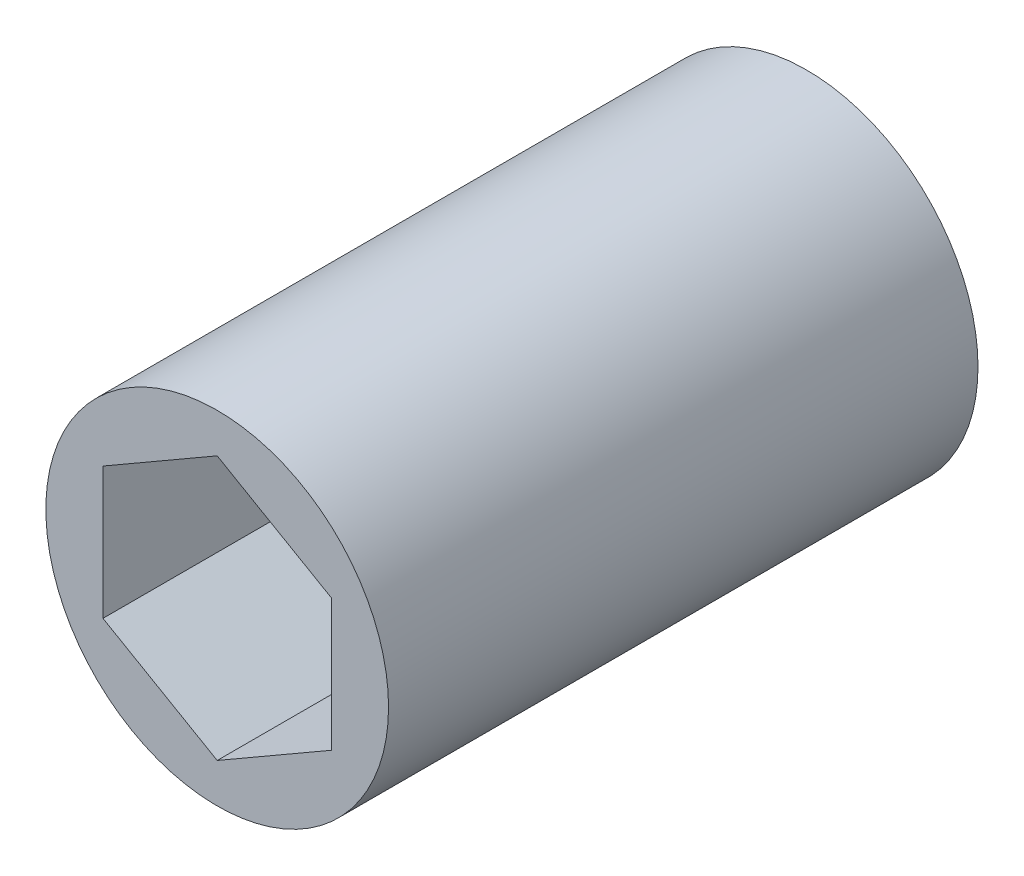
SolidWorks part; units mm, degrees
material "PET"
ref_plane "Front Plane" through (0, 0, 0) normal (0, 0, 1) x (1, 0, 0)
ref_plane "Top Plane" through (0, 0, 0) normal (0, 1, 0) x (1, 0, 0)
ref_plane "Right Plane" through (0, 0, 0) normal (1, 0, 0) x (0, 0, -1)
sketch "Sketch1" plane through (0, 0, 0) normal (0, 0, 1) x (1, 0, 0)
  line L0 (-6.35, -3.6662) -> (-8.2489, -4.7625) construction
  line L1 (6.35, -3.6662) -> (6.35, 3.6662)
  line L2 (6.35, 3.6662) -> (0, 7.3323)
  line L3 (0, 7.3323) -> (-6.35, 3.6662)
  line L4 (-6.35, 3.6662) -> (-6.35, -3.6662)
  line L5 (-6.35, -3.6662) -> (0, -7.3323)
  line L6 (0, -7.3323) -> (6.35, -3.6662)
  line L7 (-8.2489, -4.7625) -> (8.2489, 4.7625) construction
  circle A0 centre (0, 0) radius 9.525
  circle A1 centre (0, 0) radius 6.35 construction
  dimension "D1" = 19.05
  dimension "D2" = 12.7
  dimension "D3" = 16.4978
extrude "Boss-Extrude1" add sketch "Sketch1" along normal blind 32.766
